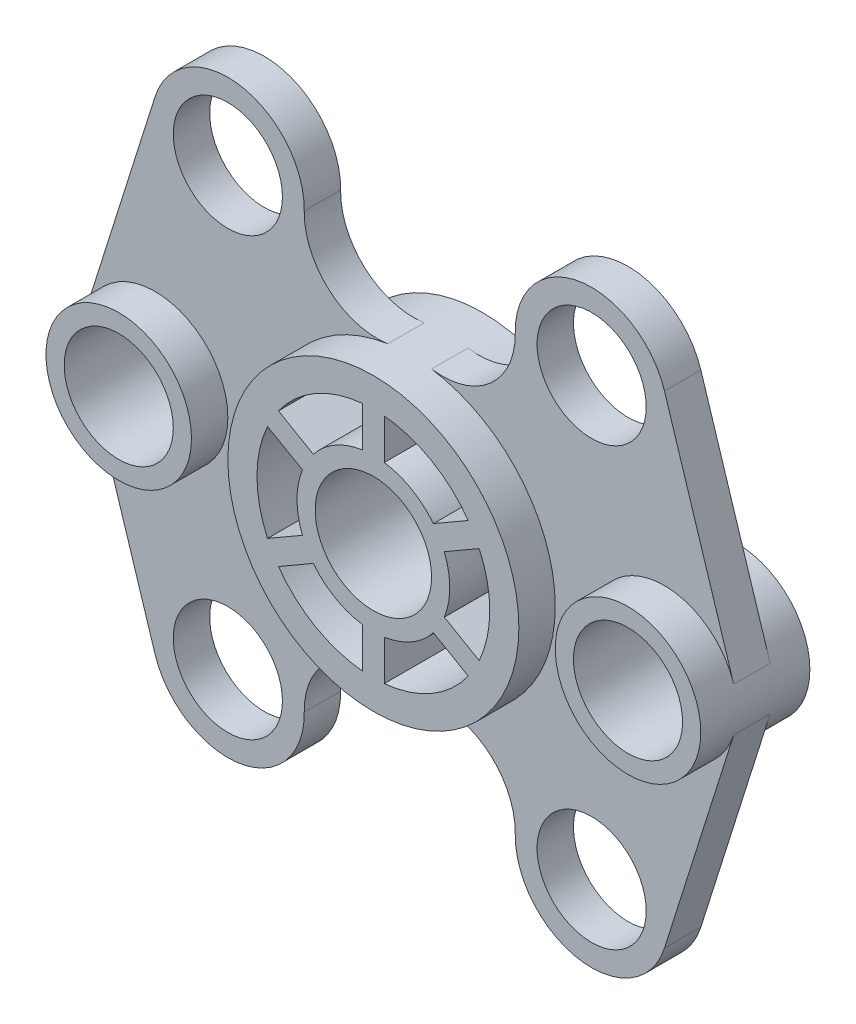
SolidWorks part; units mm, degrees
ref_plane "Front Plane" through (0, 0, 0) normal (0, 0, 1) x (1, 0, 0)
ref_plane "Top Plane" through (0, 0, 0) normal (0, 1, 0) x (1, 0, 0)
ref_plane "Right Plane" through (0, 0, 0) normal (1, 0, 0) x (0, 0, -1)
sketch "Sketch1" plane through (0, 0, 0) normal (0, 0, 1) x (1, 0, 0)
  line L0 (0, 0) -> (0, 50000) construction
  line L1 (0, 0) -> (64018.328, 0) construction
  line L2 (-3, 31.8591) -> (-3, 20.7846)
  line L3 (3, 31.8591) -> (3, 20.7846)
  line L4 (29.0908, 13.3315) -> (19.5, 7.7942)
  line L5 (26.0908, 18.5276) -> (16.5, 12.9904)
  line L6 (26.0908, -18.5276) -> (16.5, -12.9904)
  line L7 (29.0908, -13.3315) -> (19.5, -7.7942)
  line L8 (-3, -31.8591) -> (-3, -20.7846)
  line L9 (3, -31.8591) -> (3, -20.7846)
  line L10 (-29.0908, -13.3315) -> (-19.5, -7.7942)
  line L11 (-26.0908, -18.5276) -> (-16.5, -12.9904)
  line L12 (-26.0908, 18.5276) -> (-16.5, 12.9904)
  line L13 (-29.0908, 13.3315) -> (-19.5, 7.7942)
  line L14 (0, -60) -> (50000, -60) construction
  line L15 (-89.0713, -6.0238) -> (-70.0249, -66.325)
  line L16 (-89.0713, 6.0238) -> (-70.0249, 66.325)
  line L17 (89.0713, 6.0238) -> (70.0249, 66.325)
  line L18 (89.0713, -6.0238) -> (70.0249, -66.325)
  circle A0 centre (0, 0) radius 16
  arc A1 (-3, 20.7846) -> (-16.5, 12.9904) centre (0, 0) ccw
  arc A2 (-3, 31.8591) -> (-26.0908, 18.5276) centre (0, 0) ccw
  circle A3 centre (0, 0) radius 40
  arc A4 (-19.5, 7.7942) -> (-19.5, -7.7942) centre (0, 0) ccw
  arc A5 (-29.0908, 13.3315) -> (-29.0908, -13.3315) centre (0, 0) ccw
  arc A6 (-16.5, -12.9904) -> (-3, -20.7846) centre (0, 0) ccw
  arc A7 (-26.0908, -18.5276) -> (-3, -31.8591) centre (0, 0) ccw
  arc A8 (3, -20.7846) -> (16.5, -12.9904) centre (0, 0) ccw
  arc A9 (3, -31.8591) -> (26.0908, -18.5276) centre (0, 0) ccw
  arc A10 (19.5, -7.7942) -> (19.5, 7.7942) centre (0, 0) ccw
  arc A11 (29.0908, -13.3315) -> (29.0908, 13.3315) centre (0, 0) ccw
  arc A12 (16.5, 12.9904) -> (3, 20.7846) centre (0, 0) ccw
  arc A13 (26.0908, 18.5276) -> (3, 31.8591) centre (0, 0) ccw
  circle A14 centre (-70, 0) radius 20
  circle A15 centre (-70, 0) radius 15
  circle A16 centre (-50, -60) radius 15
  arc A17 (-71, -60) -> (-29.0029, -59.6519) centre (-50, -60) ccw
  arc A18 (-6.0038, -39.5469) -> (-28.9941, -60) centre (-9.0056, -59.3203) ccw
  circle A19 centre (-50, 60) radius 15
  arc A20 (-6.0038, 39.5469) -> (-28.9941, 60) centre (-9.0056, 59.3203) cw
  arc A21 (-71, 60) -> (-29.0029, 59.6519) centre (-50, 60) cw
  arc A22 (71, 60) -> (29.0029, 59.6519) centre (50, 60) ccw
  arc A23 (6.0038, 39.5469) -> (28.9941, 60) centre (9.0056, 59.3203) ccw
  circle A24 centre (50, 60) radius 15
  arc A25 (6.0038, -39.5469) -> (28.9941, -60) centre (9.0056, -59.3203) cw
  arc A26 (71, -60) -> (29.0029, -59.6519) centre (50, -60) cw
  circle A27 centre (50, -60) radius 15
  circle A28 centre (70, 0) radius 15
  circle A29 centre (70, 0) radius 20
  point P35 (0, 0)
  dimension "D1" = 32
  dimension "D2" = 42
  dimension "D3" = 64
  dimension "D4" = 80
  dimension "D7" = 30
  dimension "D8" = 40
  dimension "D9" = 30
  dimension "D10" = 42
  dimension "D14" = 40
  dimension "D5" = 6
  dimension "D11" = 60
  dimension "D12" = 50
  dimension "D13" = 20
  dimension "D6" = 6
extrude "Boss-Extrude1" add sketch "Sketch1" along normal mid plane 30 contours A14 A15 | A3 A13 L5 A12 L3 A11 L7 A10 L4 A9 L9 A8 L6 A7 L11 A6 L8 A5 L13 A4 L10 A0 A2 L2 A1 L12 | A29 A28 region at (-89.4343, 0, 0) region at (-38.8686, 0, 0) region at (50.5657, 0, 0)
extrude "Boss-Extrude2" add sketch "Sketch1<3>" along normal mid plane 10 contours L18 A29 L17 A22 A23 A3 A25 A26 A24 A27 | A21 L16 A14 L15 A17 A18 A3 A20 A16 A19 region at (-66.6751, -21.5658, 0) region at (31.7133, -27.2622, 0)
sketch "Sketch1<3>" plane through (0, 0, 0) normal (0, 0, 1) x (1, 0, 0) same geometry as "Sketch1"
